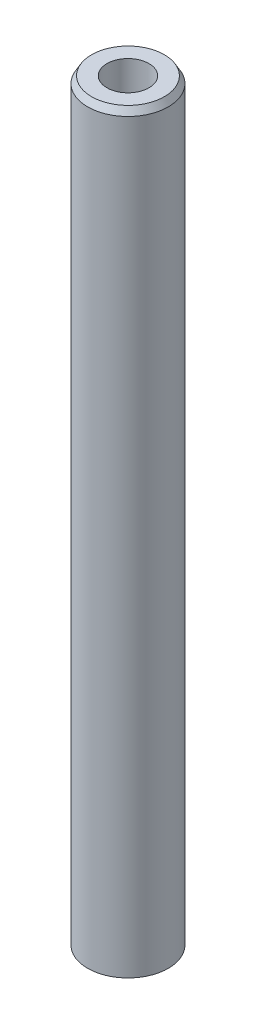
SolidWorks part; units mm, degrees
ref_plane "Front Plane" through (0, 0, 0) normal (0, 0, 1) x (1, 0, 0)
ref_plane "Top Plane" through (0, 0, 0) normal (0, 1, 0) x (1, 0, 0)
ref_plane "Right Plane" through (0, 0, 0) normal (1, 0, 0) x (0, 0, -1)
sketch "Sketch1" plane through (0, 0, 0) normal (0, 1, 0) x (1, 0, 0)
  circle A0 centre (0, 0) radius 5
  dimension "SHAFT_OD" = 10
extrude "Boss-Extrude1" add sketch "Sketch1" along normal blind 93.849
sketch "Sketch2" plane through (0, 0, 0) normal (0, 1, 0) x (1, 0, 0)
  circle A0 centre (0, 0) radius 2.6066
  dimension "BORE_D" = 5.2132
extrude "Cut-Extrude1" cut sketch "Sketch2" along normal through all
chamfer "Chamfer1" distance 0.8471 angle 30 2 edges at (0, 93.849, 5) (0, 0, 5) first distance on face at (0, 93.849, 5) first distance on face at (0, 0, 2.6066)
